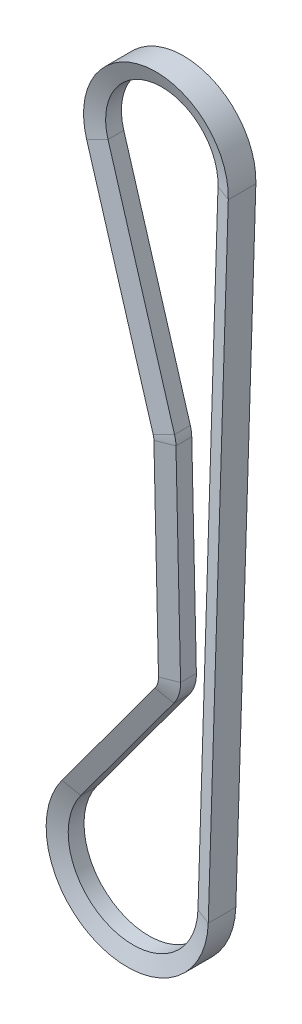
SolidWorks part; units mm, degrees
ref_plane "Front Plane" through (0, 0, 0) normal (0, 0, 1) x (1, 0, 0)
ref_plane "Top Plane" through (0, 0, 0) normal (0, 1, 0) x (1, 0, 0)
ref_plane "Right Plane" through (0, 0, 0) normal (1, 0, 0) x (0, 0, -1)
sketch "Sketch2" plane through (0, 0, 0) normal (0, 0, 1) x (1, 0, 0)
  line L0 (0, 0) -> (1, 0) construction
  line L1 (0, 0) -> (0, 1) construction
  line L12 (24.9876, -0.7869) -> (18.0632, -220.6575)
  line L14 (-32.476, -203.1822) -> (-0.3465, -159.5145)
  line L15 (0.8872, -155.6069) -> (-0.7039, -85.6249)
  line L16 (-0.9689, -83.9484) -> (-23.9502, -7.1686)
  arc A4 (18.0632, -220.6575) -> (-32.476, -203.1822) centre (-9.9229, -219.7761) cw
  arc A7 (-23.9502, -7.1686) -> (24.9876, -0.7869) centre (0, 0) cw
  arc A8 (-0.3465, -159.5145) -> (0.8872, -155.6069) centre (-5.4612, -155.7512) ccw
  arc A9 (-0.7039, -85.6249) -> (-0.9689, -83.9484) centre (-7.0523, -85.7693) ccw
ref_plane "Plane4" through (-23.9502, -7.1686, 0) normal (-0.2867, 0.958, 0) x (0.958, 0.2867, 0)
sketch "Sketch3" plane through (-23.9502, -7.1686, 0) normal (-0.2867, 0.958, 0) x (0.958, 0.2867, 0)
  line L0 (0, -4.7625) -> (0, 4.7625)
  line L1 (0, -4.7625) -> (5.588, -2.7286)
  line L2 (5.588, -2.7286) -> (5.588, 2.7286)
  line L3 (5.588, 2.7286) -> (0, 4.7625)
  line L4 (0, 0) -> (5.588, 0) construction
  dimension "D1" = 9.525
  dimension "D2" = 5.588
  dimension "D3" = 40
sweep "Sweep1" add profiles "Sketch3" path "Sketch2"
